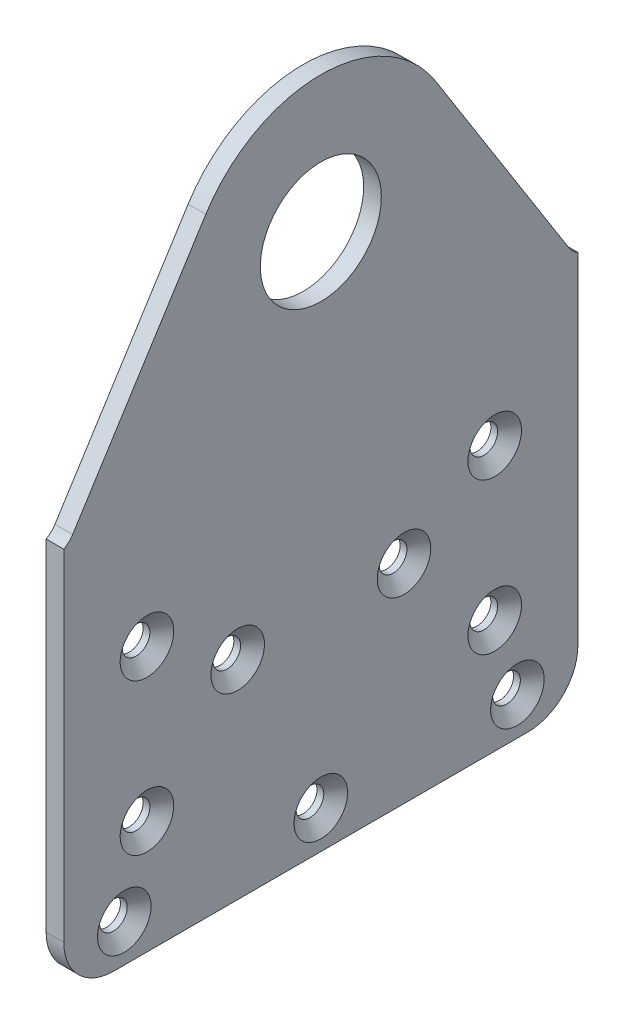
SolidWorks part; units mm, degrees
material "6061-T6 (SS)"
ref_plane "Front" through (0, 0, 0) normal (0, 0, 1) x (1, 0, 0)
ref_plane "Top" through (0, 0, 0) normal (0, 1, 0) x (1, 0, 0)
ref_plane "Right" through (0, 0, 0) normal (1, 0, 0) x (0, 0, -1)
ref_axis "side-side" through (80.9, 0, 0) along (-1, 0, 0)
ref_axis "up-down" through (0, 50, 0) along (0, -1, 0)
ref_axis "front-back" through (0, 0, -80.9) along (0, 0, 1)
sketch "Sketch2" plane through (0, 0, 0) normal (1, 0, 0) x (0, 0, -1)
  line L0 (-26, -66) -> (-23, -56) construction
  line L1 (-23, -56) -> (-23, -36) construction
  line L2 (-23, -36) -> (-11, -43.5) construction
  line L6 (-34, -71) -> (34, -71)
  line L7 (-34, 9.857) -> (-34, -71)
  line L8 (34, -71) -> (34, 9.857)
  line L9 (-11, -43.5) -> (0, -66) construction
  arc A1 (31.3633, -18.902) -> (34, -21.0753) centre (35.5091, -16.5582) ccw
  circle A2 centre (0, 0) radius 4
  arc A4 (34, 9.857) -> (-34, 9.857) centre (0, 0) ccw
sketch "Sketch1" plane through (0, 0, 0) normal (1, 0, 0) x (0, 0, -1)
  line L0 (0, 0) -> (-27.9363, -5.6405) construction
  line L2 (-15.2172, 9.6145) -> (-32.825, -18.2541)
  line L4 (15.2172, 9.6145) -> (32.825, -18.2541)
  line L5 (-34, -71) -> (34, -71) construction
  line L6 (-34, -19.3516) -> (-34, -71)
  line L8 (0, -71.96) -> (0, -41.7737) construction
  line L9 (34, -19.3516) -> (34, -71)
  line L11 (-34, -71) -> (34, -71)
  line L12 (0, 50) -> (0, -50) construction
  arc A0 (-15.2172, 9.6145) -> (15.2172, 9.6145) centre (0, 0) cw
  circle A1 centre (0, 0) radius 8
  arc A6 (0.5117, 28.4954) -> (-27.9363, -5.6405) centre (0, 0) ccw construction
  arc A8 (-34, -19.3516) -> (-32.825, -18.2541) centre (-35.5091, -16.5582) ccw
  arc A11 (32.825, -18.2541) -> (34, -19.3516) centre (35.5091, -16.5582) ccw
  circle A14 centre (-23, -56) radius 1.3525 construction
  circle A15 centre (-23, -36) radius 1.3525 construction
  arc A16 (31.3633, -18.902) -> (34, -21.0753) centre (35.5091, -16.5582) ccw construction
  point P8 (34, -71)
  point P9 (0, 0)
  point P12 (-17.984, 0.7599)
  point P19 (0, 0)
  point P20 (-40.6419, -71)
  point P23 (0, 0)
  point P28 (0, 0)
  point P30 (0, 0)
  point P33 (-23, -56)
  point P34 (0, 0)
  point P35 (15.619, 8.947)
  point P36 (0, 0)
  point P38 (-23, -36)
  point P40 (18.0401, -5.6405)
  point P41 (18, -5.6405)
  point P42 (21.175, -8.8155)
  point P43 (27.7811, -6.1435)
  point P44 (30.4249, -15.888)
  point P48 (34, -10.9935)
  dimension "D1" = 16
  dimension "D2" = 10
  dimension "D4" = 3.175
  dimension "D3" = 28.5
  dimension "D9" = 101.415
  dimension "D10" = 68
extrude "Boss-Extrude1" add sketch "Sketch1" along normal blind 2.3368
hole_wizard "CSK for #6 Flat Head Machine Screw (100)1" positions "Sketch3" profile "Sketch4" countersink size "#6" standard "ANSI Inch" end condition through all
sketch "Sketch3" plane through (2.3368, 0, 0) normal (1, 0, 0) x (0, 0, -1)
  line L0 (0, 0) -> (0, 43.4307) construction
  point P0 (-26, -66)
  point P3 (-23, -56)
  point P6 (-23, -36)
  point P9 (-11, -43.5)
  point P12 (0, -66)
  point P18 (0, 0)
  point P19 (26, -66)
  point P20 (23, -56)
  point P21 (11, -43.5)
  point P22 (23, -36)
sketch "Sketch4" plane through (2.3368, -66, 26) normal (0, 1, 0) x (0, 0, -1)
  line L0 (0, 0) -> (0, 2.3368)
  line L1 (0, 2.3368) -> (1.8288, 2.3368)
  line L2 (1.8288, 2.3368) -> (1.8288, 1.4386)
  line L3 (1.8288, 1.4386) -> (3.5433, 0)
  line L5 (3.5433, 0) -> (0, 0)
  line L6 (-1.8288, 1.4386) -> (-3.5433, 0) construction
  line L11 (0, -6.35) -> (0, 107.95) construction
  dimension "Thru Hole Dia." = 3.6576
  dimension "Thru Hole Depth" = 2.3368
  dimension "Near C'Sink Dia." = 7.0866
  dimension "Near C'Sink Angle" = 100
fillet "Fillet1" radius 6.6 2 edges at (1.1684, -71, -34) (1.1684, -71, 34)
